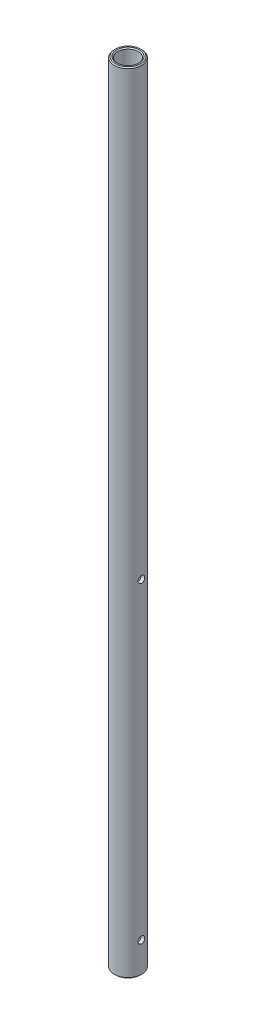
SolidWorks part; units mm, degrees
material "AISI 304"
ref_plane "Спереди" through (0, 0, 0) normal (0, 0, 1) x (1, 0, 0)
ref_plane "Сверху" through (0, 0, 0) normal (0, 1, 0) x (1, 0, 0)
ref_plane "Справа" through (0, 0, 0) normal (1, 0, 0) x (0, 0, -1)
other "Configuration Table"
sketch "Эскиз1" plane through (0, 0, 0) normal (0, 1, 0) x (1, 0, 0)
  circle A0 centre (0, 0) radius 4
  circle A1 centre (0, 0) radius 3
  dimension "D1" = 8
  dimension "D2" = 6
extrude "Бобышка-Вытянуть1" add sketch "Эскиз1" along normal blind 230
chamfer "Фаска1" distance 0.3 angle 45 4 edges at (0, 230, 3) (0, 0, 3) (0, 0, 4) (0, 230, 4)
sketch "Эскиз2" plane through (0, 0, 0) normal (1, 0, 0) x (0, 0, -1)
  circle A0 centre (0, 9) radius 1 construction
  circle A1 centre (0, 9) radius 1
extrude "Вырез-Вытянуть1" cut sketch "Эскиз2" against normal through all both and the other way through all
sketch "Эскиз3" plane through (0, 0, 0) normal (1, 0, 0) x (0, 0, -1)
  circle A0 centre (0, 100) radius 1.25 construction
  circle A1 centre (0, 100) radius 1.25 construction
  circle A2 centre (0, 100) radius 1
  circle A3 centre (0, 9) radius 1 construction
  circle A4 centre (0, 9) radius 1 construction
extrude "Вырез-Вытянуть2" cut sketch "Эскиз3" against normal through all both and the other way through all
